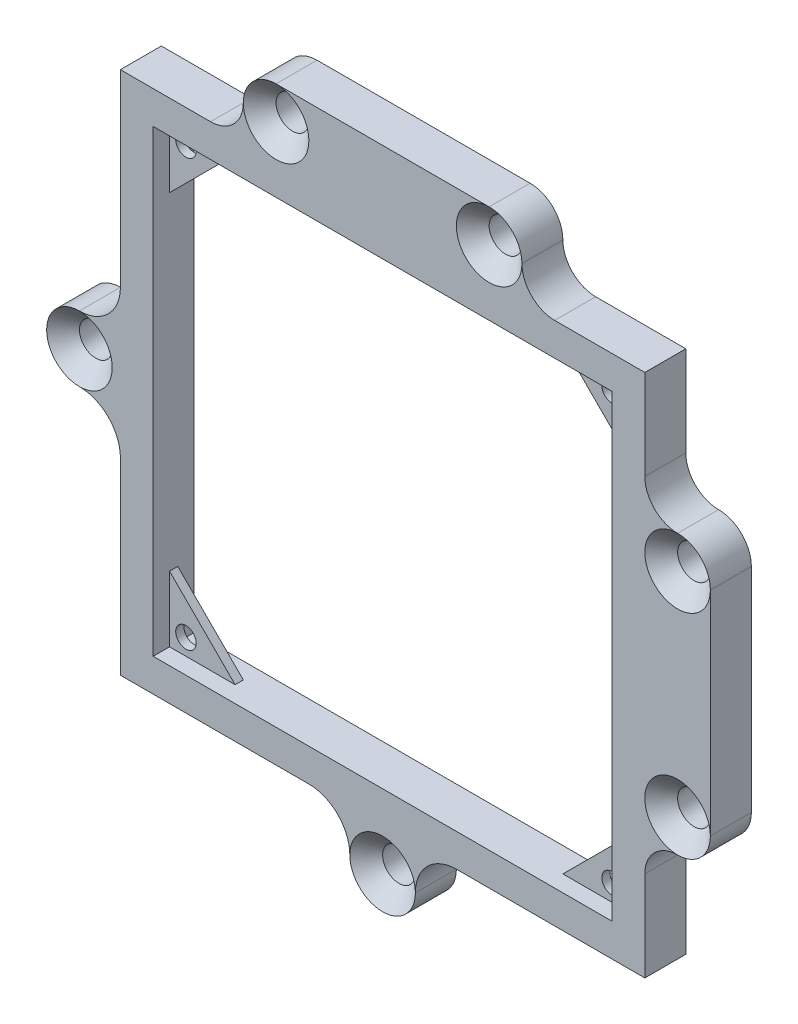
SolidWorks part; units mm, degrees
ref_plane "Top Plane" through (0, 0, 0) normal (0, 0, 1) x (1, 0, 0)
ref_plane "Right Plane" through (0, 0, 0) normal (0, 1, 0) x (1, 0, 0)
ref_plane "Front Plane" through (0, 0, 0) normal (1, 0, 0) x (0, 0, -1)
sketch "Sketch1" plane through (0, 0, 0) normal (0, 0, 1) x (1, 0, 0)
  line L44 (40, -13) -> (40, -9) construction
  line L47 (28, -28) -> (-28, -28) construction
  line L48 (-28, -28) -> (-28, 28) construction
  line L49 (-28, 28) -> (-9, 28) construction
  line L52 (-21, 32) -> (-32, 32) construction
  line L53 (-32, 32) -> (-32, 9) construction
  line L54 (-32, -9) -> (-32, -32) construction
  line L55 (-32, -32) -> (-9, -32) construction
  line L56 (9, -32) -> (32, -32) construction
  line L57 (32, -32) -> (32, -21) construction
  line L60 (32, 21) -> (32, 32) construction
  line L61 (32, 32) -> (21, 32) construction
  line L62 (13, 40) -> (9, 40) construction
  line L65 (28, 28) -> (28, 9) construction
  line L66 (40, -13) -> (40, 13)
  line L69 (28, -28) -> (-28, -28)
  line L70 (-28, -28) -> (-28, 28)
  line L71 (-28, 28) -> (28, 28)
  line L74 (-21, 32) -> (-32, 32)
  line L75 (-32, 32) -> (-32, 9)
  line L76 (-32, -9) -> (-32, -32)
  line L77 (-32, -32) -> (-9, -32)
  line L78 (9, -32) -> (32, -32)
  line L79 (32, -32) -> (32, -21)
  line L82 (32, 21) -> (32, 32)
  line L83 (32, 32) -> (21, 32)
  line L84 (13, 40) -> (-13, 40)
  line L87 (28, 28) -> (28, -28)
  arc A40 (36, -17) -> (40, -13) centre (36, -13) ccw construction
  arc A41 (-13, 40) -> (-17, 36) centre (-13, 36) ccw construction
  arc A42 (-21, 32) -> (-17, 36) centre (-21, 36) ccw construction
  arc A43 (-37, 4) -> (-32, 9) centre (-37, 9) ccw construction
  arc A44 (-37, 4) -> (-37, -4) centre (-37, 0) ccw construction
  arc A45 (-32, -9) -> (-37, -4) centre (-37, -9) ccw construction
  arc A46 (-4, -37) -> (-9, -32) centre (-9, -37) ccw construction
  arc A47 (-4, -37) -> (4, -37) centre (0, -37) ccw construction
  arc A48 (9, -32) -> (4, -37) centre (9, -37) ccw construction
  arc A49 (36, -17) -> (32, -21) centre (36, -21) ccw construction
  arc A50 (40, 13) -> (36, 17) centre (36, 13) ccw construction
  arc A51 (32, 21) -> (36, 17) centre (36, 21) ccw construction
  arc A52 (17, 36) -> (21, 32) centre (21, 36) ccw construction
  arc A53 (17, 36) -> (13, 40) centre (13, 36) ccw construction
  arc A54 (36, -17) -> (40, -13) centre (36, -13) ccw
  arc A55 (-13, 40) -> (-17, 36) centre (-13, 36) ccw
  arc A56 (-21, 32) -> (-17, 36) centre (-21, 36) ccw
  arc A57 (-37, 4) -> (-32, 9) centre (-37, 9) ccw
  arc A58 (-37, 4) -> (-37, -4) centre (-37, 0) ccw
  arc A59 (-32, -9) -> (-37, -4) centre (-37, -9) ccw
  arc A60 (-4, -37) -> (-9, -32) centre (-9, -37) ccw
  arc A61 (-4, -37) -> (4, -37) centre (0, -37) ccw
  arc A62 (9, -32) -> (4, -37) centre (9, -37) ccw
  arc A63 (36, -17) -> (32, -21) centre (36, -21) ccw
  arc A64 (40, 13) -> (36, 17) centre (36, 13) ccw
  arc A65 (32, 21) -> (36, 17) centre (36, 21) ccw
  arc A66 (17, 36) -> (21, 32) centre (21, 36) ccw
  arc A67 (17, 36) -> (13, 40) centre (13, 36) ccw
  circle A68 centre (-37, 0) radius 2 construction
  circle A69 centre (-13, 36) radius 2 construction
  circle A70 centre (0, -37) radius 2 construction
  circle A71 centre (36, -13) radius 2 construction
  circle A72 centre (36, 13) radius 2 construction
  circle A73 centre (13, 36) radius 2 construction
  circle A74 centre (-37, 0) radius 2
  circle A75 centre (-13, 36) radius 2
  circle A76 centre (0, -37) radius 2
  circle A77 centre (36, -13) radius 2
  circle A78 centre (36, 13) radius 2
  circle A79 centre (13, 36) radius 2
  point P6 (40, 12.5995)
  point P14 (28, -27.0566)
  point P16 (-12.5146, 40)
  point P46 (-4, 40)
  point P53 (27.5114, 28)
extrude "Boss-Extrude1" add sketch "Sketch1" along normal blind 5
chamfer "Chamfer1" distance 2 angle 45 6 edges at (15, 36, 5) (-11, 36, 5) (-35, 0, 5) (38, -13, 5) (2, -37, 5) (38, 13, 5)
ref_plane "Plane1" through (0, 0, 2.5) normal (0, 0, 1) x (1, 0, 0)
sketch "Sketch2" plane through (0, 0, 2.5) normal (0, 0, 1) x (1, 0, 0)
  line L0 (20, 28) -> (28, 20)
  line L1 (28, 20) -> (28, 28)
  line L2 (28, 28) -> (20, 28)
  line L3 (24, 28) -> (26, 26) construction
  line L4 (26, 26) -> (28, 24) construction
  line L6 (24, 24) -> (26, 26) construction
  circle A0 centre (26, 26) radius 1.25
  dimension "D1" = 8
  dimension "D2" = 2.5
extrude "Boss-Extrude2" add sketch "Sketch2" along normal mid plane 1
ref_axis "Axis1" through (0, 0, 5.25) along (0, 0, -1)
pattern_circular "CirPattern1" count 4 every 90 about axis through (0, 0, 5.25) along (0, 0, -1) of "Boss-Extrude2"
